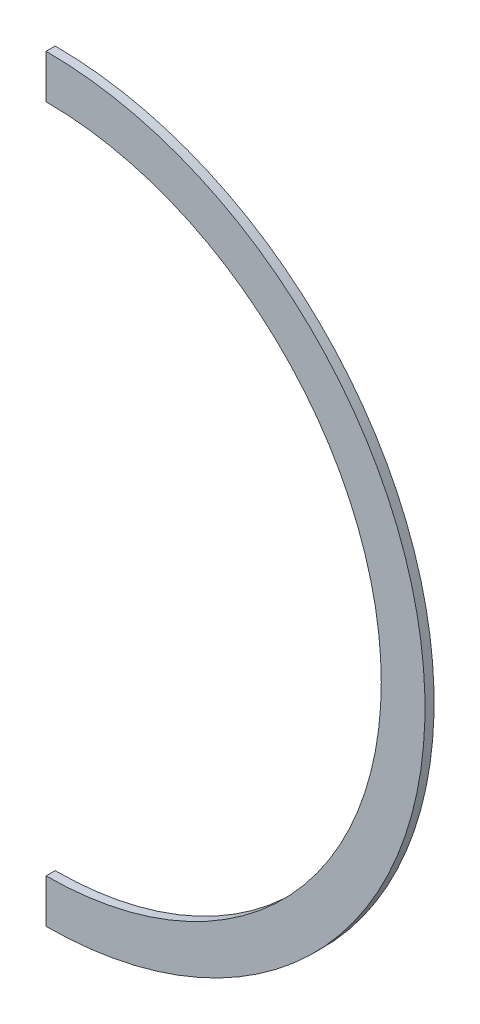
SolidWorks part; units mm, degrees
material "Balsa"
ref_plane "Front Plane" through (0, 0, 0) normal (0, 0, 1) x (1, 0, 0)
ref_plane "Top Plane" through (0, 0, 0) normal (0, 1, 0) x (1, 0, 0)
ref_plane "Right Plane" through (0, 0, 0) normal (1, 0, 0) x (0, 0, -1)
sketch "Sketch2" plane through (0, 0, 0) normal (0, 0, 1) x (1, 0, 0)
  line L0 (0, 0) -> (0, 236.6718) construction
  line L1 (-1.651, 128.5137) -> (-1.651, 121.4017) construction
  line L3 (1.651, 128.5137) -> (1.651, 121.4017) construction
  line L4 (-1.651, 121.4017) -> (1.651, 121.4017) construction
  line L5 (-136.2076, -77.8947) -> (0.0002, 0.7357) construction
  line L6 (-136.2076, -77.8947) -> (0.0002, 0.7357) construction
  line L7 (136.2041, -77.9016) -> (0.0002, 0.7357) construction
  line L8 (136.2041, -77.9016) -> (0.0002, 0.7357) construction
  line L9 (-116.9771, -64.8869) -> (-110.0184, -60.8698) construction
  line L10 (-115.4068, -67.7931) -> (-108.3675, -63.7295) construction
  line L11 (-110.0184, -60.8698) -> (-108.3675, -63.7295) construction
  line L12 (-117.5533, -65.2196) -> (-116.9771, -64.8869) construction
  line L13 (-115.9024, -68.0792) -> (-115.4068, -67.7931) construction
  line L14 (115.4068, -67.7931) -> (109.2475, -64.2371) construction
  line L15 (110.8985, -61.3775) -> (109.2475, -64.2371) construction
  line L16 (116.9771, -64.8869) -> (110.8985, -61.3775) construction
  arc A0 (-1.651, 128.5137) -> (-116.9771, -64.8869) centre (0, -3.556) ccw
  arc A1 (0.0665, 128.1531) -> (63.0696, -118.8475) centre (0, -3.3993) ccw construction
  circle A2 centre (0, -3.556) radius 116.84
  arc A3 (63.0696, -118.8475) -> (0.0665, 128.1531) centre (0, -3.3993) ccw construction
  arc A4 (0, 128.524) -> (-1.651, 128.5137) centre (0, -3.556) ccw
  circle A5 centre (0, -3.556) radius 132.08 construction
  arc A6 (1.651, 128.5137) -> (0, 128.524) centre (0, -3.556) ccw
  arc A7 (-116.9771, -64.8869) -> (-116.2009, -66.3452) centre (0, -3.556) ccw
  arc A8 (-115.4068, -67.7931) -> (115.4068, -67.7931) centre (0, -3.556) ccw
  arc A9 (-116.2009, -66.3452) -> (-115.4068, -67.7931) centre (0, -3.556) ccw
  arc A10 (115.4068, -67.7931) -> (116.1978, -66.3509) centre (0, -3.556) ccw
  arc A11 (116.9771, -64.8869) -> (1.651, 128.5137) centre (0, -3.556) ccw
  arc A12 (116.1978, -66.3509) -> (116.9771, -64.8869) centre (0, -3.556) ccw
  point P24 (-115.4068, -67.7931)
  dimension "D1" = 3.556
  dimension "D3" = 264.16
  dimension "D2" = 15.24
  dimension "D4" = 3.302
  dimension "D5" = 7.112
  dimension "D6" = 3.302
  dimension "D7" = 8.128
  dimension "D8" = 7.076
extrude "Boss-Extrude1" add sketch "Sketch2" along normal mid plane 3.175
sketch "Sketch3" plane through (0, 0, 0) normal (1, 0, 0) x (0, 0, -1)
  line L1 (-109.3908, 192.564) -> (122.8198, 192.564)
  line L2 (-109.3908, 192.564) -> (-109.3908, -206.3906)
  line L3 (-109.3908, -206.3906) -> (122.8198, -206.3906)
  line L4 (122.8198, 192.564) -> (122.8198, -206.3906)
extrude "Cut-Extrude1" cut sketch "Sketch3" against normal through all
